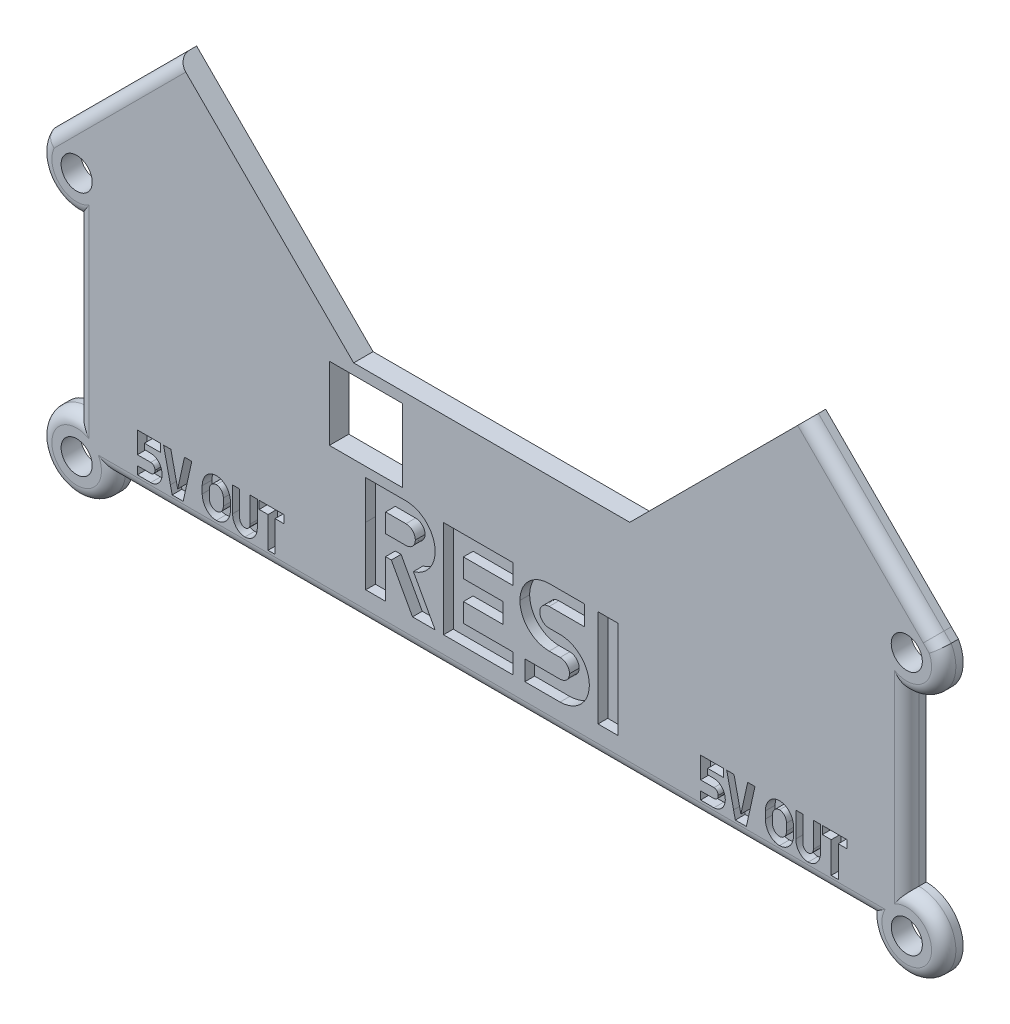
SolidWorks part; units mm, degrees
ref_plane "Front Plane" through (0, 0, 0) normal (0, 0, 1) x (1, 0, 0)
ref_plane "Top Plane" through (0, 0, 0) normal (0, 1, 0) x (1, 0, 0)
ref_plane "Right Plane" through (0, 0, 0) normal (1, 0, 0) x (0, 0, -1)
sketch "Sketch1" plane through (0, 0, 0) normal (0, 0, 1) x (1, 0, 0)
  line L0 (-32.3573, -16.1337) -> (-45.2809, -29.0573)
  line L8 (32.3573, -16.1337) -> (45.2809, -29.0573)
  line L10 (16.7466, -31.7443) -> (32.3573, -16.1337)
  line L12 (14.2027, -34.2883) -> (16.7466, -31.7443)
  line L17 (42.7, -35.4383) -> (42.7, -53.0883)
  line L19 (38.9, -56.8883) -> (-38.9, -56.8883)
  line L21 (-42.7, -53.0883) -> (-42.7, -35.4383)
  line L27 (0, -56.8883) -> (0, -34.1383) construction
  line L28 (-0.525, -56.8883) -> (0.525, -56.8883) construction
  line L29 (-42.7, -44.2633) -> (42.7, -44.2633) construction
  line L34 (-14.2027, -34.2883) -> (14.2027, -34.2883)
  line L35 (-16.7466, -31.7443) -> (-14.2027, -34.2883)
  line L36 (-16.7466, -31.7443) -> (-32.3573, -16.1337)
  line L37 (-45.2809, -29.0573) -> (-46.0284, -29.8048)
  line L38 (-14.1405, -34.1383) -> (14.1405, -34.1383) construction
  line L39 (-32.3573, -15.9215) -> (-45.387, -28.9513) construction
  line L40 (-16.6405, -31.6383) -> (-32.3573, -15.9215) construction
  line L41 (-16.6405, -31.6383) -> (-14.1405, -34.1383) construction
  line L42 (14.1405, -34.1383) -> (16.6405, -31.6383) construction
  line L43 (16.6405, -31.6383) -> (32.3573, -15.9215) construction
  line L44 (42.55, -35.2852) -> (42.55, -53.2414) construction
  line L45 (32.3573, -15.9215) -> (45.387, -28.9513) construction
  line L46 (39.0531, -56.7383) -> (-39.0531, -56.7383) construction
  line L47 (-42.55, -53.2414) -> (-42.55, -35.2852) construction
  circle A8 centre (-42.7, -31.6383) radius 1.6
  circle A9 centre (-42.7, -56.8883) radius 1.6
  circle A10 centre (42.7, -56.8883) radius 1.6
  circle A11 centre (42.7, -31.6383) radius 1.6
  arc A12 (-46.0284, -29.8048) -> (-42.7, -35.4383) centre (-42.7, -31.6383) ccw
  arc A13 (42.7, -35.4383) -> (46.0167, -29.7836) centre (42.7, -31.6383) ccw
  arc A14 (38.9, -56.8883) -> (42.7, -53.0883) centre (42.7, -56.8883) ccw
  arc A15 (-42.7, -53.0883) -> (-38.9, -56.8883) centre (-42.7, -56.8883) ccw
  arc A16 (-45.387, -28.9513) -> (-42.7, -35.4383) centre (-42.7, -31.6383) ccw construction
  arc A17 (45.2809, -29.0573) -> (46.0167, -29.7836) centre (101.9922, 27.654) ccw
  arc A18 (42.7, -35.4383) -> (45.387, -28.9513) centre (42.7, -31.6383) ccw construction
  arc A19 (42.55, -35.2852) -> (45.2809, -29.0573) centre (42.7, -31.6383) ccw construction
  arc A20 (39.0531, -56.7383) -> (42.55, -53.2414) centre (42.7, -56.8883) ccw construction
  arc A21 (-42.55, -53.2414) -> (-39.0531, -56.7383) centre (-42.7, -56.8883) ccw construction
  arc A22 (-45.2809, -29.0573) -> (-42.55, -35.2852) centre (-42.7, -31.6383) ccw construction
  dimension "D1" = 3.2
  dimension "D2" = 3.8
  dimension "D3" = 80.2019
  dimension "D4" = 14.2027
  dimension "D5" = 0.15
  dimension "D6" = 16.7466
  dimension "D7" = 32.3573
  dimension "D8" = 38.9
  dimension "D9" = 27.654
extrude "Boss-Extrude1" add sketch "Sketch1" along normal blind 2
sketch "Sketch2" plane through (0, 0, 2) normal (0, 0, 1) x (1, 0, 0)
  line L1 (-16.7, -35.3883) -> (-9.2, -35.3883)
  line L2 (-16.7, -35.3883) -> (-16.7, -42.8883)
  line L3 (-16.7, -42.8883) -> (-9.2, -42.8883)
  line L4 (-9.2, -35.3883) -> (-9.2, -42.8883)
  line L5 (-12.95, -42.8883) -> (-12.95, -35.3883) construction
  line L6 (-16.7, -39.1383) -> (-9.2, -39.1383) construction
  line L7 (-42.7, -35.4383) -> (-42.7, -53.0883) construction
  line L9 (-38.9, -56.8883) -> (38.9, -56.8883) construction
  point P0 (-12.95, -39.1383)
  dimension "D1" = 7.5
  dimension "D2" = 14
  dimension "D3" = 7.5
  dimension "D4" = 26
extrude "Cut-Extrude1" cut sketch "Sketch2" against normal up to next
sketch "Sketch3" plane through (0, 0, 2) normal (0, 0, 1) x (1, 0, 0)
  line L0 (0, -56.8883) -> (0, -34.2883) construction
  line L1 (-38.9, -56.8883) -> (38.9, -56.8883) construction
  line L2 (14.2027, -34.2883) -> (-14.2027, -34.2883) construction
  line L3 (-37.1269, -55.3883) -> (-20.8105, -55.3883) construction
  line L4 (37.1269, -55.3883) -> (20.8105, -55.3883) construction
  line L5 (-9.2, -42.8883) -> (-9.2, -35.3883) construction
  line L6 (-16.7, -42.8883) -> (-9.2, -42.8883) construction
  text T0 "5V OUT" font "BANSED" height 4
  text T1 "5V OUT" font "BANSED" height 4
  point P12 (-22.3105, -54.9983)
  point P13 (-20.8105, -54.9983)
  dimension "D2" = 34.0731
  dimension "D1" = 1.5
  dimension "D3" = 27.9269
  dimension "D4" = 12.3203
extrude "Cut-Extrude2" cut sketch "Sketch3" against normal blind 1
sketch "Sketch4" plane through (0, 0, 2) normal (0, 0, 1) x (1, 0, 0)
  line L0 (0, -56.8883) -> (0, -34.2883) construction
  line L1 (-38.9, -56.8883) -> (38.9, -56.8883) construction
  line L2 (14.2027, -34.2883) -> (-14.2027, -34.2883) construction
  line L3 (-45.0324, -53.8883) -> (45.0324, -53.8883) construction
  arc A1 (38.9, -56.8883) -> (42.7, -53.0883) centre (42.7, -56.8883) ccw construction
  arc A2 (-42.7, -53.0883) -> (-38.9, -56.8883) centre (-42.7, -56.8883) ccw construction
  text T0 "RESI" font "BANSED" height 10
  dimension "D1" = 3
extrude "Cut-Extrude3" cut sketch "Sketch4" against normal blind 1
fillet "Fillet1" radius 1.25 10 edges at (-45.9716, -33.5713, 2) (-42.7, -44.2633, 2) (-45.387, -59.5753, 2) (0, -56.8883, 2) (45.387, -59.5753, 2) (42.7, -44.2633, 2) (45.9778, -33.5608, 2) (45.6476, -29.4217, 2) (38.8191, -22.5955, 2) (-39.1928, -22.9692, 2)
